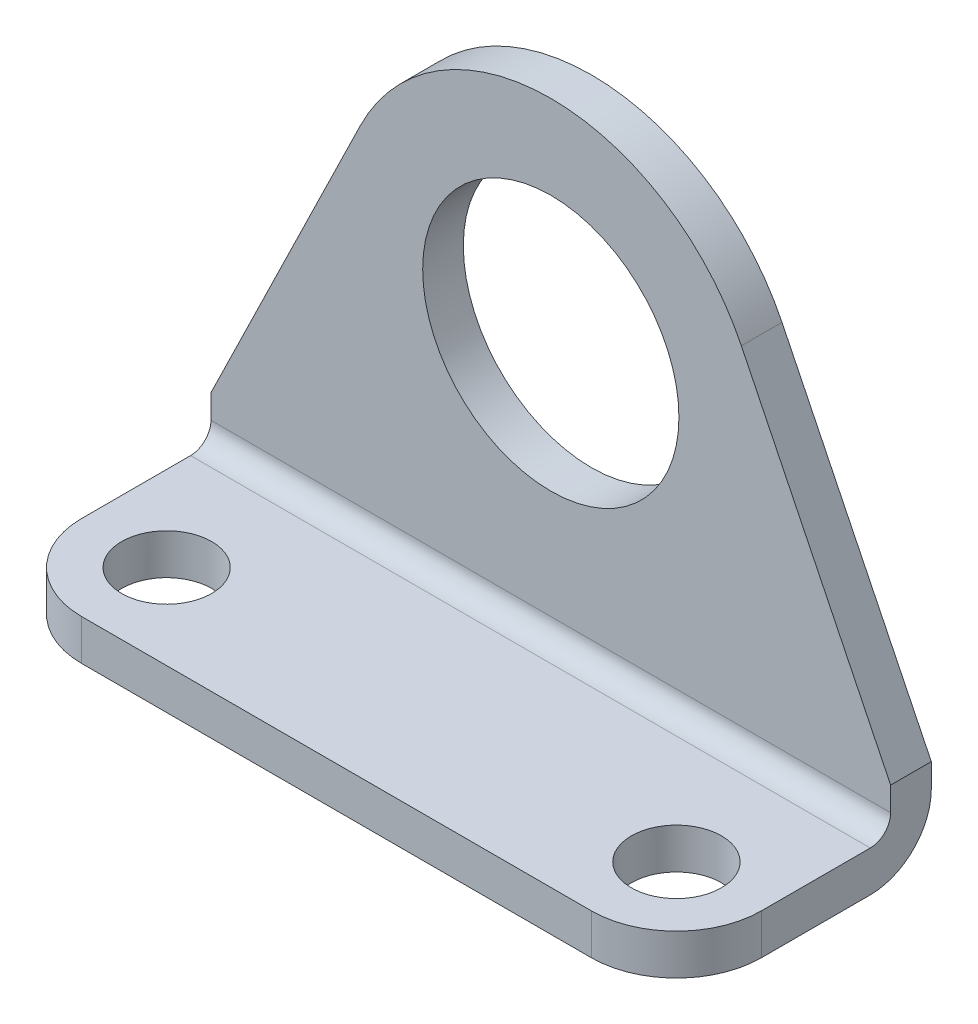
SolidWorks part; units mm, degrees
ref_plane "Front Plane" through (0, 0, 0) normal (0, 0, 1) x (1, 0, 0)
ref_plane "Top Plane" through (0, 0, 0) normal (0, 1, 0) x (1, 0, 0)
ref_plane "Right Plane" through (0, 0, 0) normal (1, 0, 0) x (0, 0, -1)
sketch "Sketch1" plane through (0, 0, 0) normal (1, 0, 0) x (0, 0, -1)
  line L0 (-9.525, 1.5189) -> (-9.525, 0)
  line L1 (-9.525, 0) -> (-2.2809, 0)
  line L2 (0, 2.2809) -> (0, 22.86)
  line L3 (0, 22.86) -> (-1.5189, 22.86)
  line L4 (-1.5189, 22.86) -> (-1.5189, 2.2809)
  line L5 (-2.2809, 1.5189) -> (-9.525, 1.5189)
  arc A0 (-2.2809, 0) -> (0, 2.2809) centre (-2.2809, 2.2809) ccw
  arc A1 (-1.5189, 2.2809) -> (-2.2809, 1.5189) centre (-2.2809, 2.2809) cw
extrude "Boss-Extrude1" add sketch "Sketch1" along normal blind 25.4
sketch "Sketch2" plane through (0, 0, 0) normal (0, 0, 1) x (1, 0, 0)
  line L0 (-5.08, 30.48) -> (-5.08, -1.905)
  line L1 (-5.08, -1.905) -> (30.48, -1.905)
  line L2 (30.48, -1.905) -> (30.48, 30.48)
  line L3 (30.48, 30.48) -> (-5.08, 30.48)
  line L4 (-1.55, 0) -> (26.95, 0)
  line L5 (26.95, 0) -> (19.8215, 14.6019)
  line L6 (5.5785, 14.6019) -> (-1.55, 0)
  arc A0 (19.8215, 14.6019) -> (5.5785, 14.6019) centre (12.7, 11.1252) ccw
extrude "Cut-Extrude1" cut sketch "Sketch2" along normal blind 2.2784
sketch "Sketch3" plane through (0, 0, 0) normal (0, 0, 1) x (1, 0, 0)
  circle A0 centre (12.7, 11.1252) radius 4.7879
extrude "Cut-Extrude2" cut sketch "Sketch3" along normal blind 2.2784
sketch "Sketch4" plane through (0, 0, 0) normal (0, 1, 0) x (1, 0, 0)
  circle A0 centre (3.175, -6.35) radius 1.6828
extrude "Cut-Extrude3" cut sketch "Sketch4" along normal blind 2.2784
sketch "Sketch5" plane through (0, 0, 0) normal (0, 1, 0) x (1, 0, 0)
  circle A0 centre (22.225, -6.35) radius 1.6828
extrude "Cut-Extrude4" cut sketch "Sketch5" along normal blind 2.2784
sketch "Sketch6" plane through (0, 0, 0) normal (0, 1, 0) x (1, 0, 0)
  line L0 (-12.7, -12.7) -> (3.175, -12.7)
  line L1 (3.175, -12.7) -> (3.175, -9.525)
  line L2 (0, -6.35) -> (-12.7, -6.35)
  line L3 (-12.7, -6.35) -> (-12.7, -12.7)
  arc A0 (3.175, -9.525) -> (0, -6.35) centre (3.175, -6.35) cw
extrude "Cut-Extrude5" cut sketch "Sketch6" along normal blind 2.2784
sketch "Sketch7" plane through (0, 0, 0) normal (0, 1, 0) x (1, 0, 0)
  line L0 (22.225, -9.525) -> (22.225, -12.7)
  line L1 (22.225, -12.7) -> (38.1, -12.7)
  line L2 (38.1, -12.7) -> (38.1, -6.35)
  line L3 (38.1, -6.35) -> (25.4, -6.35)
  arc A0 (25.4, -6.35) -> (22.225, -9.525) centre (22.225, -6.35) cw
extrude "Cut-Extrude6" cut sketch "Sketch7" along normal blind 2.2784
ref_plane "Plane1" through (25.4, 0, 0) normal (1, 0, 0) x (0, 0, -1)
ref_plane "Plane2" through (12.7, 0, 0) normal (1, 0, 0) x (0, 0, -1)
ref_plane "Plane3" through (0, 0, 1.5189) normal (0, 0, 1) x (1, 0, 0)
ref_plane "d1 XY" through (12.7, 0, 0) normal (1, 0, 0) x (0, 0, -1)
ref_plane "d1 XZ" through (0, 6.3373, 0) normal (0, -1, 0) x (-1, 0, 0)
ref_plane "d1 YZ" through (0, 0, 0) normal (0, 0, -1) x (-1, 0, 0)
ref_axis "d1 X" through (12.7, 6.3373, 80.9) along (0, 0, -1)
ref_axis "d1 Y" through (12.7, -50, 0) along (0, 1, 0)
ref_axis "d1 Z" through (80.9, 6.3373, 0) along (-1, 0, 0)
sketch3d "d1"
  point P0 (12.7, 6.3373, 0)
ref_plane "d2 XY" through (12.7, 0, 0) normal (1, 0, 0) x (0, 0, -1)
ref_plane "d2 XZ" through (0, 15.9131, 0) normal (0, -1, 0) x (-1, 0, 0)
ref_plane "d2 YZ" through (0, 0, 0) normal (0, 0, -1) x (-1, 0, 0)
ref_axis "d2 X" through (12.7, 15.9131, 80.9) along (0, 0, -1)
ref_axis "d2 Y" through (12.7, -50, 0) along (0, 1, 0)
ref_axis "d2 Z" through (80.9, 15.9131, 0) along (-1, 0, 0)
sketch3d "d2"
  point P0 (12.7, 15.9131, 0)
ref_plane "h1 XY" through (12.7, 0, 0) normal (1, 0, 0) x (0, 0, -1)
ref_plane "h1 XZ" through (0, 0, 0) normal (0, -1, 0) x (-1, 0, 0)
ref_plane "h1 YZ" through (0, 0, 9.525) normal (0, 0, -1) x (-1, 0, 0)
ref_axis "h1 X" through (12.7, 0, 80.9) along (0, 0, -1)
ref_axis "h1 Y" through (12.7, -50, 9.525) along (0, 1, 0)
ref_axis "h1 Z" through (80.9, 0, 9.525) along (-1, 0, 0)
sketch3d "h1"
  point P0 (12.7, 0, 9.525)
ref_plane "h2 XY" through (12.7, 0, 0) normal (1, 0, 0) x (0, 0, -1)
ref_plane "h2 XZ" through (0, 1.5189, 0) normal (0, -1, 0) x (-1, 0, 0)
ref_plane "h2 YZ" through (0, 0, 9.525) normal (0, 0, -1) x (-1, 0, 0)
ref_axis "h2 X" through (12.7, 1.5189, 80.9) along (0, 0, -1)
ref_axis "h2 Y" through (12.7, -50, 9.525) along (0, 1, 0)
ref_axis "h2 Z" through (80.9, 1.5189, 9.525) along (-1, 0, 0)
sketch3d "h2"
  point P0 (12.7, 1.5189, 9.525)
ref_plane "h3 XY" through (12.7, 0, 0) normal (1, 0, 0) x (0, 0, -1)
ref_plane "h3 XZ" through (0, 11.1252, 0) normal (0, -1, 0) x (-1, 0, 0)
ref_plane "h3 YZ" through (0, 0, 1.5189) normal (0, 0, -1) x (-1, 0, 0)
ref_axis "h3 X" through (12.7, 11.1252, 80.9) along (0, 0, -1)
ref_axis "h3 Y" through (12.7, -50, 1.5189) along (0, 1, 0)
ref_axis "h3 Z" through (80.9, 11.1252, 1.5189) along (-1, 0, 0)
sketch3d "h3"
  point P0 (12.7, 11.1252, 1.5189)
ref_plane "h4 XY" through (12.7, 0, 0) normal (1, 0, 0) x (0, 0, -1)
ref_plane "h4 XZ" through (0, 19.05, 0) normal (0, -1, 0) x (-1, 0, 0)
ref_plane "h4 YZ" through (0, 0, 1.5189) normal (0, 0, -1) x (-1, 0, 0)
ref_axis "h4 X" through (12.7, 19.05, 80.9) along (0, 0, -1)
ref_axis "h4 Y" through (12.7, -50, 1.5189) along (0, 1, 0)
ref_axis "h4 Z" through (80.9, 19.05, 1.5189) along (-1, 0, 0)
sketch3d "h4"
  point P0 (12.7, 19.05, 1.5189)
ref_plane "h5 XY" through (25.4, 0, 0) normal (1, 0, 0) x (0, 0, -1)
ref_plane "h5 XZ" through (0, 3.175, 0) normal (0, -1, 0) x (-1, 0, 0)
ref_plane "h5 YZ" through (0, 0, 0) normal (0, 0, -1) x (-1, 0, 0)
ref_axis "h5 X" through (25.4, 3.175, 80.9) along (0, 0, -1)
ref_axis "h5 Y" through (25.4, -50, 0) along (0, 1, 0)
ref_axis "h5 Z" through (80.9, 3.175, 0) along (-1, 0, 0)
sketch3d "h5"
  point P0 (25.4, 3.175, 0)
ref_plane "h6 XY" through (25.4, 0, 0) normal (1, 0, 0) x (0, 0, -1)
ref_plane "h6 XZ" through (0, 0, 0) normal (0, -1, 0) x (-1, 0, 0)
ref_plane "h6 YZ" through (0, 0, 0) normal (0, 0, -1) x (-1, 0, 0)
ref_axis "h6 X" through (25.4, 0, 80.9) along (0, 0, -1)
ref_axis "h6 Y" through (25.4, -50, 0) along (0, 1, 0)
ref_axis "h6 Z" through (80.9, 0, 0) along (-1, 0, 0)
sketch3d "h6"
  point P0 (25.4, 0, 0)
ref_plane "l1 XY" through (0, 0, 0) normal (0, 1, 0) x (1, 0, 0)
ref_plane "l1 XZ" through (0, 0, 0) normal (0, 0, 1) x (1, 0, 0)
ref_plane "l1 YZ" through (0, 0, 0) normal (1, 0, 0) x (0, 0, -1)
ref_axis "l1 X" through (-80.9, 0, 0) along (1, 0, 0)
ref_axis "l1 Y" through (0, 0, 50) along (0, 0, -1)
ref_axis "l1 Z" through (0, 50, 0) along (0, -1, 0)
sketch3d "l1"
  point P0 (0, 0, 0)
ref_plane "l2 XY" through (0, 0, 0) normal (0, 1, 0) x (1, 0, 0)
ref_plane "l2 XZ" through (0, 0, 0) normal (0, 0, 1) x (1, 0, 0)
ref_plane "l2 YZ" through (25.4, 0, 0) normal (1, 0, 0) x (0, 0, -1)
ref_axis "l2 X" through (-80.9, 0, 0) along (1, 0, 0)
ref_axis "l2 Y" through (25.4, 0, 50) along (0, 0, -1)
ref_axis "l2 Z" through (25.4, 50, 0) along (0, -1, 0)
sketch3d "l2"
  point P0 (25.4, 0, 0)
ref_plane "l3 XY" through (0, 0, 0) normal (0, 1, 0) x (1, 0, 0)
ref_plane "l3 XZ" through (0, 0, 9.525) normal (0, 0, 1) x (1, 0, 0)
ref_plane "l3 YZ" through (0, 0, 0) normal (1, 0, 0) x (0, 0, -1)
ref_axis "l3 X" through (-80.9, 0, 9.525) along (1, 0, 0)
ref_axis "l3 Y" through (0, 0, 50) along (0, 0, -1)
ref_axis "l3 Z" through (0, 50, 9.525) along (0, -1, 0)
sketch3d "l3"
  point P0 (0, 0, 9.525)
ref_plane "l4 XY" through (0, 0, 0) normal (0, 1, 0) x (1, 0, 0)
ref_plane "l4 XZ" through (0, 0, 6.35) normal (0, 0, 1) x (1, 0, 0)
ref_plane "l4 YZ" through (0, 0, 0) normal (1, 0, 0) x (0, 0, -1)
ref_axis "l4 X" through (-80.9, 0, 6.35) along (1, 0, 0)
ref_axis "l4 Y" through (0, 0, 50) along (0, 0, -1)
ref_axis "l4 Z" through (0, 50, 6.35) along (0, -1, 0)
sketch3d "l4"
  point P0 (0, 0, 6.35)
ref_plane "l5 XY" through (0, 0, 0) normal (0, 1, 0) x (1, 0, 0)
ref_plane "l5 XZ" through (0, 0, 6.35) normal (0, 0, 1) x (1, 0, 0)
ref_plane "l5 YZ" through (3.175, 0, 0) normal (1, 0, 0) x (0, 0, -1)
ref_axis "l5 X" through (-80.9, 0, 6.35) along (1, 0, 0)
ref_axis "l5 Y" through (3.175, 0, 50) along (0, 0, -1)
ref_axis "l5 Z" through (3.175, 50, 6.35) along (0, -1, 0)
sketch3d "l5"
  point P0 (3.175, 0, 6.35)
ref_plane "l6 XY" through (0, 0, 0) normal (0, 1, 0) x (1, 0, 0)
ref_plane "l6 XZ" through (0, 0, 6.35) normal (0, 0, 1) x (1, 0, 0)
ref_plane "l6 YZ" through (22.225, 0, 0) normal (1, 0, 0) x (0, 0, -1)
ref_axis "l6 X" through (-80.9, 0, 6.35) along (1, 0, 0)
ref_axis "l6 Y" through (22.225, 0, 50) along (0, 0, -1)
ref_axis "l6 Z" through (22.225, 50, 6.35) along (0, -1, 0)
sketch3d "l6"
  point P0 (22.225, 0, 6.35)
ref_plane "l7 XY" through (0, 0, 0) normal (0, 1, 0) x (1, 0, 0)
ref_plane "l7 XZ" through (0, 0, 8.0328) normal (0, 0, 1) x (1, 0, 0)
ref_plane "l7 YZ" through (22.225, 0, 0) normal (1, 0, 0) x (0, 0, -1)
ref_axis "l7 X" through (-80.9, 0, 8.0328) along (1, 0, 0)
ref_axis "l7 Y" through (22.225, 0, 50) along (0, 0, -1)
ref_axis "l7 Z" through (22.225, 50, 8.0328) along (0, -1, 0)
sketch3d "l7"
  point P0 (22.225, 0, 8.0328)
ref_plane "l8 XY" through (0, 0, 0) normal (0, 1, 0) x (1, 0, 0)
ref_plane "l8 XZ" through (0, 0, 4.6673) normal (0, 0, 1) x (1, 0, 0)
ref_plane "l8 YZ" through (22.225, 0, 0) normal (1, 0, 0) x (0, 0, -1)
ref_axis "l8 X" through (-80.9, 0, 4.6673) along (1, 0, 0)
ref_axis "l8 Y" through (22.225, 0, 50) along (0, 0, -1)
ref_axis "l8 Z" through (22.225, 50, 4.6673) along (0, -1, 0)
sketch3d "l8"
  point P0 (22.225, 0, 4.6673)
ref_plane "mounting_bracket XY" through (0, 0, 1.5189) normal (0, 0, 1) x (1, 0, 0)
ref_plane "mounting_bracket XZ" through (0, 11.1252, 0) normal (0, -1, 0) x (-1, 0, 0)
ref_plane "mounting_bracket YZ" through (12.7, 0, 0) normal (1, 0, 0) x (0, 0, -1)
ref_axis "mounting_bracket X" through (-80.9, 11.1252, 1.5189) along (1, 0, 0)
ref_axis "mounting_bracket Y" through (12.7, -50, 1.5189) along (0, 1, 0)
ref_axis "mounting_bracket Z" through (12.7, 11.1252, 80.9) along (0, 0, -1)
sketch3d "mounting_bracket"
  point P0 (12.7, 11.1252, 1.5189)
ref_plane "mounting_bracket_1 XY" through (0, 0, 0) normal (0, 0, 1) x (1, 0, 0)
ref_plane "mounting_bracket_1 XZ" through (0, 11.1252, 0) normal (0, -1, 0) x (-1, 0, 0)
ref_plane "mounting_bracket_1 YZ" through (12.7, 0, 0) normal (1, 0, 0) x (0, 0, -1)
ref_axis "mounting_bracket_1 X" through (-80.9, 11.1252, 0) along (1, 0, 0)
ref_axis "mounting_bracket_1 Y" through (12.7, -50, 0) along (0, 1, 0)
ref_axis "mounting_bracket_1 Z" through (12.7, 11.1252, 80.9) along (0, 0, -1)
sketch3d "mounting_bracket_1"
  point P0 (12.7, 11.1252, 0)
